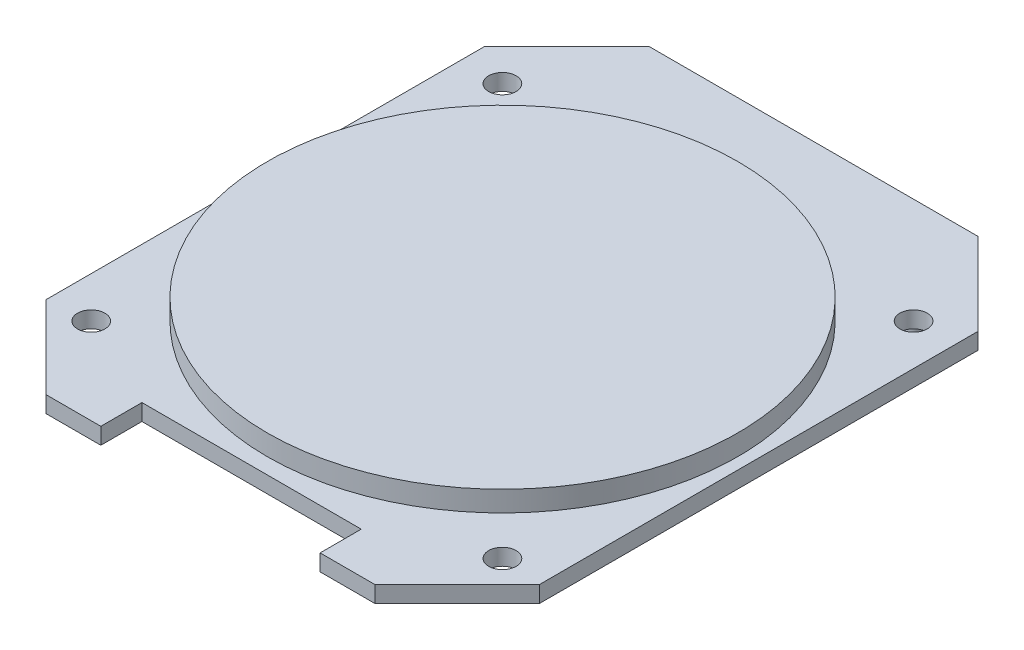
SolidWorks part; units mm, degrees
ref_plane "前视基准面" through (0, 0, 0) normal (0, 0, 1) x (1, 0, 0)
ref_plane "上视基准面" through (0, 0, 0) normal (0, 1, 0) x (1, 0, 0)
ref_plane "右视基准面" through (0, 0, 0) normal (1, 0, 0) x (0, 0, -1)
sketch "草图1" plane through (0, 0, 0) normal (0, 1, 0) x (1, 0, 0)
  line L0 (0, 0) -> (0, 34.4262) construction
  line L1 (-12, 44) -> (12, 44)
  line L2 (12, 44) -> (18, 38)
  line L3 (18, 38) -> (18, 6)
  line L4 (18, 6) -> (12, 0)
  line L5 (12, 0) -> (8, 0)
  line L6 (8, 0) -> (8, 3)
  line L7 (8, 3) -> (-8, 3)
  line L8 (15, 6.3) -> (15, 57.1325) construction
  line L9 (-8, 0) -> (-8, 3)
  line L10 (-12, 0) -> (-8, 0)
  line L11 (-18, 6) -> (-12, 0)
  line L12 (-18, 38) -> (-18, 6)
  line L13 (-12, 44) -> (-18, 38)
  circle A0 centre (15, 6.3) radius 1
  circle A1 centre (15, 36.3) radius 1
  circle A2 centre (-15, 6.3) radius 1
  circle A3 centre (-15, 36.3) radius 1
  point P19 (0, 3)
  point P28 (0, 44)
  dimension "D8" = 2
  dimension "D9" = 3
  dimension "D12" = 2
  dimension "D1" = 18
  dimension "D2" = 44
  dimension "D3" = 6
  dimension "D4" = 45
  dimension "D5" = 45
  dimension "D6" = 3
  dimension "D7" = 4
  dimension "D10" = 6.3
  dimension "D11" = 7.7
extrude "凸台-拉伸1" add sketch "草图1" along normal blind 1.2
sketch "草图2" plane through (0, 1.2, 0) normal (0, 1, 0) x (1, 0, 0)
  line L0 (18, 21.31) -> (-18, 21.31) construction
  line L4 (12, 44) -> (-12, 44) construction
  line L5 (0, 0) -> (0, 45.8273) construction
  circle A0 centre (0, 21.31) radius 17.16
  dimension "D1" = 34.32
  dimension "D2" = 22.69
extrude "凸台-拉伸2" add sketch "草图2" along normal blind 1.5
sketch "草图3" plane through (0, 0, 0) normal (0, -1, 0) x (1, 0, 0)
  line L0 (0, -44) -> (0, 0) construction
  line L1 (6, -32.5) -> (-6, -32.5)
  line L2 (6, -32.5) -> (6, -28)
  line L3 (6, -28) -> (-6, -28)
  line L5 (12, -44) -> (-12, -44) construction
  line L6 (-6, -32.5) -> (-6, -28)
  line L7 (-8, -3) -> (8, -3) construction
  line L8 (-11.43, -44) -> (-11.43, -41.46)
  line L9 (11.43, -44) -> (-11.43, -44)
  line L10 (11.43, -44) -> (11.43, -41.46)
  line L11 (11.43, -41.46) -> (-11.43, -41.46)
  point P11 (0, -28)
  point P12 (0, -32.5)
  point P18 (0, -41.46)
  point P19 (0, -44)
  dimension "D1" = 4.5
  dimension "D2" = 25
  dimension "D3" = 12
  dimension "D4" = 2.54
  dimension "D5" = 22.86
extrude "凸台-拉伸3" add sketch "草图3" along normal blind 2
sketch "草图4" plane through (0, 0, 0) normal (0, -1, 0) x (1, 0, 0)
  line L0 (0, 0) -> (0, -45.8273) construction
  line L1 (11.1109, -42.5) -> (-17.9409, -42.5) construction
  line L2 (12, -44) -> (11.43, -44) construction
  circle A0 centre (-1.27, -42.5) radius 0.5
  circle A1 centre (-3.81, -42.5) radius 0.5
  circle A2 centre (-6.35, -42.5) radius 0.5
  circle A3 centre (-8.89, -42.5) radius 0.5
  circle A4 centre (8.89, -42.5) radius 0.5
  circle A5 centre (6.35, -42.5) radius 0.5
  circle A6 centre (3.81, -42.5) radius 0.5
  circle A7 centre (1.27, -42.5) radius 0.5
  dimension "D1" = 2.54
  dimension "D2" = 2.54
  dimension "D3" = 2.54
  dimension "D5" = 1
  dimension "D6" = 1
  dimension "D7" = 1
  dimension "D8" = 1
  dimension "D4" = 1.27
  dimension "D9" = 1.5
extrude "凸台-拉伸4" add sketch "草图4" along normal blind 8
sketch "草图5" plane through (0, 2.7, 0) normal (0, 1, 0) x (1, 0, 0)
  text T0 "<b>Smart Knob</b>\r\n<b>  Simple</b>"
